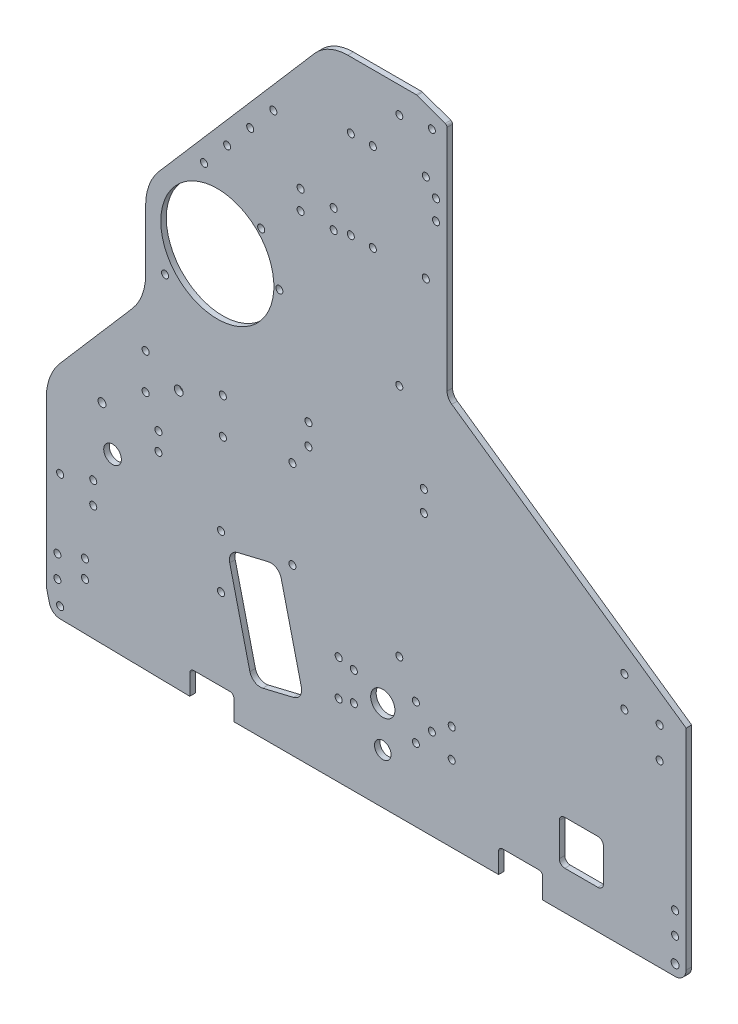
SolidWorks part; units mm, degrees
ref_plane "Front Plane" through (0, 0, 0) normal (0, 0, 1) x (1, 0, 0)
ref_plane "Top Plane" through (0, 0, 0) normal (0, 1, 0) x (1, 0, 0)
ref_plane "Right Plane" through (0, 0, 0) normal (1, 0, 0) x (0, 0, -1)
sketch "Sketch1" plane through (0, 0, 0) normal (0, 0, 1) x (1, 0, 0)
  line L0 (82.55, -20.32) -> (82.55, -6.35)
  line L2 (0, 0) -> (0, 157.48)
  line L4 (368.3, -20.32) -> (368.3, 106.68)
  line L5 (82.55, -6.35) -> (107.95, -6.35)
  line L6 (107.95, -6.35) -> (107.95, -20.32)
  line L7 (107.95, -20.32) -> (260.35, -20.32)
  line L8 (260.35, -20.32) -> (260.35, -6.35)
  line L9 (260.35, -6.35) -> (285.75, -6.35)
  line L10 (285.75, -6.35) -> (285.75, -20.32)
  line L11 (285.75, -20.32) -> (368.3, -20.32)
  line L12 (361.95, 12.7) -> (368.3, 12.7) construction
  line L13 (0, 0) -> (6.35, 0) construction
  line L14 (0.1896, -7.8901) -> (1.7771, -14.2401)
  line L15 (7.8295, -19.0491) -> (82.55, -20.32)
  line L16 (0, 0) -> (0, -6.35)
  line L17 (76.2, 128.905) -> (79.375, 128.905) construction
  line L18 (57.15, 118.5863) -> (101.6, 118.5862) construction
  line L19 (57.15, 118.5863) -> (57.15, 139.2238) construction
  line L20 (101.6, 118.5862) -> (101.6, 139.2237) construction
  line L21 (57.15, 139.2238) -> (101.6, 139.2237) construction
  line L22 (57.15, 118.5863) -> (101.6, 139.2237) construction
  line L23 (101.6, 118.5862) -> (57.15, 139.2238) construction
  line L25 (203.2, 59.805) -> (203.2, 194.805) construction
  line L26 (203.2, 194.805) -> (203.2, 329.805) construction
  line L27 (355.6, 332.105) -> (330.2, 332.105) construction
  line L28 (330.2, 332.105) -> (330.2, 217.805) construction
  line L29 (330.2, 217.805) -> (355.6, 217.805) construction
  line L30 (355.6, 217.805) -> (355.6, 332.105) construction
  line L31 (203.2, 344.805) -> (203.2, 194.805) construction
  line L32 (50.8, 332.105) -> (76.2, 332.105) construction
  line L33 (76.2, 332.105) -> (76.2, 217.805) construction
  line L34 (50.8, 217.805) -> (50.8, 332.105) construction
  line L35 (76.2, 217.805) -> (50.8, 217.805) construction
  line L36 (213.2, 344.805) -> (230.6638, 338.455)
  line L37 (203.2, 344.805) -> (161.925, 344.805)
  line L38 (203.2, 344.805) -> (213.2, 344.805)
  line L39 (348.5362, 344.805) -> (413.4623, 344.805)
  line L40 (348.5362, 344.805) -> (230.6638, 344.805) construction
  line L42 (161.925, 344.805) -> (0, 157.48)
  line L44 (230.6638, 338.455) -> (230.6638, 202.565)
  line L45 (230.6638, 202.565) -> (368.3, 106.68)
  line L46 (213.2, 344.805) -> (-141.0713, 344.805) construction
  circle A0 centre (6.35, 0) radius 2.032
  circle A1 centre (6.35, 12.7) radius 2.032
  circle A2 centre (361.95, 0) radius 2.032
  circle A3 centre (361.95, 12.7) radius 2.032
  arc A5 (1.7771, -14.2401) -> (7.8295, -19.0491) centre (7.9375, -12.7) ccw
  circle A6 centre (7.9375, -12.7) radius 2.032
  arc A7 (0, -6.35) -> (0.1896, -7.8901) centre (6.35, -6.35) ccw
  circle A8 centre (38.1, 78.105) radius 5.08
  circle A9 centre (76.2, 128.905) radius 2.54
  circle A10 centre (101.6, 118.5862) radius 2.032
  circle A11 centre (101.6, 139.2237) radius 2.032
  circle A12 centre (57.15, 139.2238) radius 2.032
  circle A13 centre (57.15, 118.5863) radius 2.032
  circle A15 centre (203.2, 59.805) radius 2
  circle A16 centre (203.2, 194.805) radius 2
  circle A17 centre (203.2, 329.805) radius 2
  circle A18 centre (63.5, 313.055) radius 2.032
  circle A20 centre (355.6, 332.105) radius 2.032
  circle A21 centre (330.2, 332.105) radius 2.032
  circle A22 centre (355.6, 217.805) radius 2.032
  circle A23 centre (330.2, 217.805) radius 2.032
  circle A24 centre (50.8, 332.105) radius 2.032
  circle A25 centre (76.2, 332.105) radius 2.032
  circle A26 centre (50.8, 217.805) radius 2.032
  circle A27 centre (76.2, 217.805) radius 2.032
  circle A28 centre (221.9319, 332.105) radius 2
  circle A29 centre (224.3138, 298.831) radius 2.032
  circle A30 centre (353.06, 100.7351) radius 2.032
  circle A31 centre (332.74, 115.9751) radius 2.032
  circle A32 centre (332.74, 98.1951) radius 2.032
  circle A33 centre (353.06, 82.9551) radius 2.032
  circle A34 centre (117.3562, 280.4276) radius 2.032
  circle A35 centre (104.0678, 265.0548) radius 2.032
  circle A36 centre (90.7795, 249.682) radius 2.032
  circle A38 centre (130.6445, 295.8004) radius 2.032
  circle A39 centre (68.326, 182.9237) radius 2.032
  circle A40 centre (224.3138, 287.401) radius 2.032
  point P82 (203.2, 344.805)
  point P83 (221.9319, 341.63)
  point P90 (368.3, 62.484)
  dimension "D6" = 4.064
  dimension "D10" = 6.35
  dimension "D11" = 4.064
  dimension "D17" = 38.1
  dimension "D27" = 4
  dimension "D31" = 4.064
  dimension "D32" = 41.275
  dimension "D36" = 4.064
  dimension "D47" = 39.624
  dimension "D48" = 4.064
  dimension "D25" = 5.08
  dimension "D26" = 4.064
  dimension "D52" = 4.064
  dimension "D65" = 4.064
  dimension "D69" = 10.16
  dimension "D2" = 127
  dimension "D3" = 13.97
  dimension "D4" = 25.4
  dimension "D5" = 152.4
  dimension "D7" = 12.7
  dimension "D8" = 6.35
  dimension "D9" = 20.32
  dimension "D12" = 12.7
  dimension "D13" = 1.5875
  dimension "D14" = 82.55
  dimension "D15" = 368.3
  dimension "D16" = 6.35
  dimension "D18" = 98.425
  dimension "D19" = 38.1
  dimension "D20" = 50.8
  dimension "D21" = 3.175
  dimension "D22" = 270
  dimension "D23" = 20.6375
  dimension "D24" = 44.45
  dimension "D28" = 135
  dimension "D29" = 12.7
  dimension "D30" = 15
  dimension "D33" = 63.5
  dimension "D34" = 27.4638
  dimension "D35" = 12.7
  dimension "D37" = 114.3
  dimension "D38" = 25.4
  dimension "D39" = 12.7
  dimension "D40" = 157.48
  dimension "D41" = 142.24
  dimension "D42" = 365.125
  dimension "D43" = 10
  dimension "D44" = 6.35
  dimension "D45" = 31.75
  dimension "D46" = 6.35
  dimension "D49" = 6.35
  dimension "D50" = 203.2
  dimension "D51" = 15.24
  dimension "D53" = 17.78
  dimension "D54" = 17.78
  dimension "D55" = 20.32
  dimension "D56" = 15.24
  dimension "D57" = 92.202
  dimension "D58" = 8.382
  dimension "D59" = 20.32
  dimension "D60" = 20.32
  dimension "D61" = 8.382
  dimension "D62" = 20.32
  dimension "D63" = 8.382
  dimension "D64" = 8.382
  dimension "D66" = 35.052
  dimension "D67" = 68.326
  dimension "D68" = 11.43
extrude "Boss-Extrude1" add sketch "Sketch1" along normal blind 3.175 contours L16 A7 L14 A5 L15 L2 A0 A1 A6 region at (171.4477, 119.565, 0)
fillet "Fillet1" radius 2.286 4 edges at (285.75, -6.35, 1.5875) (107.95, -6.35, 1.5875) (260.35, -6.35, 1.5875) (82.55, -6.35, 1.5875)
fillet "Fillet2" radius 6.35 1 edges at (230.6638, 202.565, 1.5875)
sketch "Sketch2" plane through (0, 0, 0) normal (0, 0, -1) x (-1, 0, 0)
  circle A0 centre (-100.5528, 71.086) radius 2.032 construction
  circle A1 centre (-100.5528, 40.606) radius 2.032 construction
  circle A2 centre (-22.225, 18.2025) radius 2.032 construction
  circle A3 centre (-22.225, 8.0425) radius 2.032 construction
  circle A4 centre (-100.5528, 71.086) radius 2.032
  circle A5 centre (-100.5528, 40.606) radius 2.032
  circle A6 centre (-22.225, 18.2025) radius 2.032
  circle A7 centre (-22.225, 8.0425) radius 2.032
extrude "Cut-Extrude1" cut sketch "Sketch2" against normal through all
fillet "Fillet3" radius 1.5875 2 edges at (230.6638, 338.455, 1.5875) (213.2, 344.805, 1.5875)
sketch "Sketch3" plane through (0, 0, 3.175) normal (0, 0, 1) x (1, 0, 0)
  line L0 (132.9524, 63.2646) -> (132.7215, 64.2281) construction
  line L1 (128.3814, 66.8897) -> (110.6828, 62.6472) construction
  line L2 (114.5132, 58.4237) -> (126.8822, 61.3887) construction
  line L3 (108.0212, 58.3071) -> (108.2522, 57.3436) construction
  line L4 (131.2006, 57.703) -> (140.0164, 20.9265) construction
  line L5 (144.0993, 16.7636) -> (132.9524, 63.2646) construction
  line L6 (108.2522, 57.3436) -> (119.3991, 10.8426) construction
  line L7 (121.1509, 16.4042) -> (112.3351, 53.1807) construction
  line L8 (119.3991, 10.8426) -> (119.6301, 9.8791) construction
  line L9 (144.3303, 15.8001) -> (144.0993, 16.7636) construction
  line L10 (137.8383, 15.6835) -> (125.4694, 12.7185) construction
  line L11 (123.9701, 7.2175) -> (141.6687, 11.4601) construction
  line L12 (132.9524, 63.2646) -> (132.7215, 64.2281)
  line L13 (128.3814, 66.8897) -> (110.6828, 62.6472)
  line L14 (114.5132, 58.4237) -> (126.8822, 61.3887)
  line L15 (108.0212, 58.3071) -> (108.2522, 57.3436)
  line L16 (131.2006, 57.703) -> (140.0164, 20.9265)
  line L17 (144.0993, 16.7636) -> (132.9524, 63.2646)
  line L18 (108.2522, 57.3436) -> (119.3991, 10.8426)
  line L19 (121.1509, 16.4042) -> (112.3351, 53.1807)
  line L20 (119.3991, 10.8426) -> (119.6301, 9.8791)
  line L21 (144.3303, 15.8001) -> (144.0993, 16.7636)
  line L22 (137.8383, 15.6835) -> (125.4694, 12.7185)
  line L23 (123.9701, 7.2175) -> (141.6687, 11.4601)
  line L24 (127.7894, 69.3598) -> (110.0908, 65.1172)
  line L25 (105.5512, 57.715) -> (105.7822, 56.7515)
  line L26 (105.7822, 56.7515) -> (116.9291, 10.2505)
  line L27 (116.9291, 10.2505) -> (117.16, 9.287)
  line L28 (124.5622, 4.7475) -> (142.2608, 8.99)
  line L29 (146.8003, 16.3922) -> (146.5694, 17.3557)
  line L30 (146.5694, 17.3557) -> (135.4225, 63.8567)
  line L31 (135.4225, 63.8567) -> (135.1915, 64.8202)
  line L32 (14.605, -0.1369) -> (103.7278, 32.3011) construction
  line L33 (14.605, -0.1369) -> (103.7278, 32.3011)
  line L34 (0, -6.35) -> (0, 157.48) construction
  line L35 (-39.6666, 74.7152) -> (103.7278, 126.9065) construction
  line L36 (26.9875, 46.9531) -> (26.9875, 59.6531) construction
  line L37 (107.95, -20.32) -> (260.35, -20.32) construction
  line L38 (64.5259, 92.5258) -> (64.5259, 102.9405) construction
  arc A0 (132.7215, 64.2281) -> (128.6308, 66.9403) centre (129.2206, 63.3889) ccw construction
  arc A1 (110.6828, 62.6472) -> (110.4377, 62.5791) centre (111.522, 59.1463) ccw construction
  arc A2 (128.6308, 66.9403) -> (128.3814, 66.8897) centre (129.2206, 63.3889) ccw construction
  arc A3 (110.4377, 62.5791) -> (108.0212, 58.3071) centre (111.522, 59.1463) ccw construction
  arc A4 (119.6301, 9.8791) -> (123.7207, 7.1669) centre (123.1309, 10.7183) ccw construction
  arc A5 (141.9139, 11.5281) -> (144.3303, 15.8001) centre (140.8295, 14.9609) ccw construction
  arc A6 (141.6687, 11.4601) -> (141.9139, 11.5281) centre (140.8295, 14.9609) ccw construction
  arc A7 (123.7207, 7.1669) -> (123.9701, 7.2175) centre (123.1309, 10.7183) ccw construction
  arc A8 (132.7215, 64.2281) -> (128.6308, 66.9403) centre (129.2206, 63.3889) ccw
  arc A9 (110.6828, 62.6472) -> (110.4377, 62.5791) centre (111.522, 59.1463) ccw
  arc A10 (128.6308, 66.9403) -> (128.3814, 66.8897) centre (129.2206, 63.3889) ccw
  arc A11 (110.4377, 62.5791) -> (108.0212, 58.3071) centre (111.522, 59.1463) ccw
  arc A12 (119.6301, 9.8791) -> (123.7207, 7.1669) centre (123.1309, 10.7183) ccw
  arc A13 (141.9139, 11.5281) -> (144.3303, 15.8001) centre (140.8295, 14.9609) ccw
  arc A14 (141.6687, 11.4601) -> (141.9139, 11.5281) centre (140.8295, 14.9609) ccw
  arc A15 (123.7207, 7.1669) -> (123.9701, 7.2175) centre (123.1309, 10.7183) ccw
  arc A16 (110.0908, 65.1172) -> (109.6726, 65.0012) centre (111.522, 59.1463) ccw
  arc A17 (109.6726, 65.0012) -> (105.5512, 57.715) centre (111.522, 59.1463) ccw
  arc A18 (117.16, 9.287) -> (124.1369, 4.6613) centre (123.1309, 10.7183) ccw
  arc A19 (124.1369, 4.6613) -> (124.5622, 4.7475) centre (123.1309, 10.7183) ccw
  arc A20 (142.2608, 8.99) -> (142.6789, 9.1061) centre (140.8295, 14.9609) ccw
  arc A21 (142.6789, 9.1061) -> (146.8003, 16.3922) centre (140.8295, 14.9609) ccw
  arc A22 (135.1915, 64.8202) -> (128.2147, 69.446) centre (129.2206, 63.3889) ccw
  arc A23 (128.2147, 69.446) -> (127.7894, 69.3598) centre (129.2206, 63.3889) ccw
  circle A26 centre (134.1438, 208.2281) radius 2.032 construction
  circle A33 centre (26.9875, 46.9531) radius 2.032
  circle A34 centre (26.9875, 59.6531) radius 2.032
  circle A35 centre (7.9375, 53.3031) radius 2.032
  circle A37 centre (32.0306, 100.8109) radius 31.75 construction
  circle A38 centre (32.0306, 100.8109) radius 2.286
  circle A39 centre (123.682, 233.4851) radius 2.032 construction
  circle A40 centre (64.5259, 102.9405) radius 2.032
  circle A41 centre (64.5259, 92.5258) radius 2.032
  circle A42 centre (134.1438, 208.2281) radius 2.032
  circle A43 centre (123.682, 233.4851) radius 2.032
  ellipse E0 centre (124.5974, 48.8487) end of major axis (128.5376, 61.3578) minor radius 6 (131.2006, 57.703) -> (126.8822, 61.3887) ccw construction
  ellipse E1 centre (122.2349, 48.2824) end of major axis (113.0518, 57.6456) minor radius 6 (114.5132, 58.4237) -> (112.3351, 53.1807) ccw construction
  ellipse E2 centre (127.7541, 25.2585) end of major axis (131.6942, 37.7675) minor radius 6 (121.1509, 16.4042) -> (125.4694, 12.7185) ccw construction
  ellipse E3 centre (130.1166, 25.8248) end of major axis (139.2998, 16.4616) minor radius 6 (137.8383, 15.6835) -> (140.0164, 20.9265) ccw construction
  ellipse E4 centre (124.5974, 48.8487) end of major axis (120.6573, 36.3397) minor radius 6 (131.2006, 57.703) -> (126.8822, 61.3887) ccw
  ellipse E5 centre (122.2349, 48.2824) end of major axis (131.4181, 38.9192) minor radius 6 (114.5132, 58.4237) -> (112.3351, 53.1807) ccw
  ellipse E6 centre (127.7541, 25.2585) end of major axis (131.6942, 37.7675) minor radius 6 (121.1509, 16.4042) -> (125.4694, 12.7185) ccw
  ellipse E7 centre (130.1166, 25.8248) end of major axis (139.2998, 16.4616) minor radius 6 (137.8383, 15.6835) -> (140.0164, 20.9265) ccw
  point P93 (26.9875, 53.3031)
  point P115 (32.0306, 100.8109)
  dimension "D3" = 63.5
  dimension "D4" = 4.572
  dimension "D8" = 4.064
  dimension "D2" = 88.9
  dimension "D5" = 7.9375
  dimension "D6" = 19.05
  dimension "D7" = 73.6231
  dimension "D9" = 12.7
  dimension "D10" = 10.4147
  dimension "D11" = 37.5384
  dimension "D12" = 45.5727
  dimension "D1" = 2.54
extrude "Cut-Extrude2" cut sketch "Sketch3" against normal through all contours A22 A23 L24 A16 A17 L25 L26 L27 A18 A19 L28 A20 A21 L29 L30 L31 A15 A12 L20 L18 L15 A11 A9 L13 A10 A8 L12 L17 L21 A13 A14 L23 | A12 A15 L23 A14 A13 L21 L17 L12 A8 A10 L13 A9 A11 L15 L18 L20 E7 L22 E6 L19 E5 L14 E4 L16 | L22 E7 L16 E4 L14 E5 L19 E6 | A38 | A41 | A40 | A35 | A34 | A33 | A43 | A42 region at (137.844, 39.8506, 3.175) region at (126.1758, 37.0536, 3.175) region at (128.1544, 68.6507, 3.175) region at (32.0306, 100.8109, 3.175) region at (64.5259, 102.9405, 3.175) region at (64.5259, 92.5258, 3.175)
sketch "Sketch4" plane through (0, 0, 3.175) normal (0, 0, 1) x (1, 0, 0)
  line L0 (57.15, 139.2238) -> (101.6, 139.2237) construction
  line L1 (168.275, 21.4312) -> (212.725, 21.4312) construction
  line L2 (168.275, 21.4312) -> (168.275, 42.0687) construction
  line L3 (168.275, 42.0687) -> (212.725, 42.0687) construction
  line L4 (212.725, 21.4312) -> (212.725, 42.0687) construction
  line L5 (168.275, 21.4312) -> (212.725, 42.0687) construction
  line L6 (168.275, 42.0687) -> (212.725, 21.4312) construction
  line L7 (57.15, 118.5863) -> (57.15, 139.2238) construction
  line L8 (107.95, -20.32) -> (260.35, -20.32) construction
  line L9 (193.675, 31.75) -> (177.005, 31.75) construction
  line L10 (190.5, 31.75) -> (193.675, 31.75) construction
  line L11 (6.35, 12.7) -> (361.95, 12.7) construction
  line L12 (107.95, -6.35) -> (107.95, -20.32) construction
  line L13 (193.675, 31.75) -> (220.6625, 31.75) construction
  line L14 (177.005, 23.4569) -> (177.005, 40.0431) construction
  line L15 (213.2, 44.805) -> (193.2, 44.805) construction
  line L16 (213.2, 44.805) -> (213.2, 344.805) construction
  line L17 (213.2, 344.805) -> (193.2, 344.805) construction
  line L18 (193.2, 44.805) -> (193.2, 344.805) construction
  line L19 (213.2, 44.805) -> (193.2, 344.805) construction
  line L20 (213.2, 344.805) -> (193.2, 44.805) construction
  line L21 (226.9319, 332.105) -> (226.9319, 31.75) construction
  line L22 (237.33, 40.0431) -> (233.3612, 40.0431) construction
  line L23 (237.33, 23.4569) -> (233.3612, 23.4569) construction
  circle A0 centre (168.275, 42.0687) radius 2.032
  circle A1 centre (212.725, 42.0687) radius 2.032
  circle A2 centre (212.725, 21.4312) radius 2.032
  circle A3 centre (168.275, 21.4312) radius 2.032
  circle A4 centre (193.675, 31.75) radius 6.985
  circle A7 centre (220.6625, 31.75) radius 14.2875 construction
  circle A8 centre (193.675, 31.75) radius 12.7 construction
  circle A9 centre (177.005, 40.0431) radius 2.032
  circle A10 centre (177.005, 23.4569) radius 2.032
  circle A11 centre (237.33, 40.0431) radius 2.032 construction
  circle A12 centre (237.33, 23.4569) radius 2.032 construction
  circle A13 centre (193.675, 8.4667) radius 4.7625
  circle A14 centre (221.9319, 31.75) radius 2.032
  circle A15 centre (221.9319, 31.75) radius 5 construction
  circle A16 centre (221.9319, 332.105) radius 5 construction
  circle A17 centre (233.3612, 23.4569) radius 2.032
  circle A18 centre (233.3612, 40.0431) radius 2.032
  point P0 (190.5, 31.75)
  point P26 (203.2, 194.805)
  point P38 (177.005, 31.75)
  dimension "D1" = 4.064
  dimension "D4" = 13.97
  dimension "D7" = 9.525
  dimension "D10" = 25.4
  dimension "D11" = 28.575
  dimension "D16" = 10
  dimension "D17" = 4.064
  dimension "D18" = 10
  dimension "D2" = 52.07
  dimension "D3" = 3.175
  dimension "D5" = 82.55
  dimension "D6" = 26.9875
  dimension "D8" = 20
  dimension "D9" = 300
  dimension "D12" = 16.67
  dimension "D13" = 16.5862
  dimension "D14" = 60.325
  dimension "D15" = 23.2833
  dimension "D19" = 3.9688
extrude "Cut-Extrude3" cut sketch "Sketch4" against normal through all
sketch "Sketch5" plane through (0, 0, 0) normal (0, 0, -1) x (-1, 0, 0)
  line L0 (-57.15, 223.5947) -> (-57.15, 165.3337)
  line L1 (-161.925, 344.805) -> (-52.7201, 218.4699) construction
  line L2 (-57.15, 165.3337) -> (0, 99.219)
  line L3 (0, -6.35) -> (0, 157.48) construction
  line L5 (-50.4199, 215.8089) -> (0, 157.48) construction
  line L6 (-57.15, 223.5947) -> (0, 157.48)
  line L7 (0, 157.48) -> (0, 99.219)
  line L8 (-361.95, -13.97) -> (-368.3, -13.97) construction
  line L9 (-361.95, -13.97) -> (-361.95, -20.32) construction
  line L10 (-285.75, -20.32) -> (-368.3, -20.32) construction
  line L11 (-368.3, -20.32) -> (-368.3, 106.68) construction
  circle A0 centre (-98.425, 208.2281) radius 32.5437
  circle A2 centre (-361.95, -13.97) radius 2.286
  dimension "D3" = 65.0875
  dimension "D7" = 4.572
  dimension "D1" = 38.1
  dimension "D2" = 57.15
  dimension "D4" = 41.275
  dimension "D5" = 41.275
  dimension "D6" = 6.35
extrude "Cut-Extrude5" cut sketch "Sketch5" against normal through all contours A0 | L7 L6 L0 L2 | A2 region at (28.575, 161.4068, 0) region at (98.425, 208.2281, 0)
fillet "Fillet4" radius 31.75 3 edges at (0, 99.219, 1.5875) (57.15, 165.3337, 1.5875) (57.15, 223.5947, 1.5875)
sketch "Sketch6" plane through (0, 0, 3.175) normal (0, 0, 1) x (1, 0, 0)
  line L0 (285.75, -20.32) -> (368.3, -20.32) construction
  line L1 (298.45, 27.305) -> (317.5, 27.305)
  line L2 (295.275, 24.13) -> (295.275, 5.08)
  line L3 (298.45, 1.905) -> (317.5, 1.905)
  line L4 (320.675, 24.13) -> (320.675, 5.08)
  line L5 (295.275, 27.305) -> (320.675, 1.905) construction
  line L6 (295.275, 1.905) -> (320.675, 27.305) construction
  line L7 (368.3, -20.32) -> (368.3, 106.68) construction
  arc A0 (295.275, 5.08) -> (298.45, 1.905) centre (298.45, 5.08) ccw
  arc A1 (317.5, 1.905) -> (320.675, 5.08) centre (317.5, 5.08) ccw
  arc A2 (317.5, 27.305) -> (320.675, 24.13) centre (317.5, 24.13) cw
  arc A3 (298.45, 27.305) -> (295.275, 24.13) centre (298.45, 24.13) ccw
  point P0 (307.975, 14.605)
  dimension "D2" = 3.175
  dimension "D1" = 25.4
  dimension "D3" = 22.225
  dimension "D4" = 47.625
extrude "Cut-Extrude6" cut sketch "Sketch6" against normal through all
fillet "Fillet5" radius 25.4 1 edges at (161.925, 344.805, 1.5875)
sketch "Sketch8" plane through (0, 0, 0) normal (0, 0, -1) x (-1, 0, 0)
  circle A0 centre (-187.96, 306.705) radius 2.032 construction
  arc A1 (-176.3652, 304.9998) -> (-176.3652, 308.4102) centre (-175.26, 306.705) ccw construction
  arc A2 (-219.0586, 304.7695) -> (-219.0586, 308.6405) centre (-218.44, 306.705) ccw construction
  circle A3 centre (-205.74, 306.705) radius 2.032 construction
  arc A4 (-219.0586, 253.9695) -> (-219.0586, 257.8405) centre (-218.44, 255.905) ccw construction
  circle A5 centre (-205.74, 255.905) radius 2.032 construction
  circle A6 centre (-187.96, 255.905) radius 2.032 construction
  arc A7 (-176.3652, 254.1998) -> (-176.3652, 257.6102) centre (-175.26, 255.905) ccw construction
  circle A8 centre (-187.96, 306.705) radius 2.032
  arc A9 (-176.3652, 304.9998) -> (-176.3652, 308.4102) centre (-175.26, 306.705) ccw
  arc A10 (-219.0586, 304.7695) -> (-219.0586, 308.6405) centre (-218.44, 306.705) ccw
  circle A11 centre (-205.74, 306.705) radius 2.032
  arc A12 (-219.0586, 253.9695) -> (-219.0586, 257.8405) centre (-218.44, 255.905) ccw
  circle A13 centre (-205.74, 255.905) radius 2.032
  circle A14 centre (-187.96, 255.905) radius 2.032
  arc A15 (-176.3652, 254.1998) -> (-176.3652, 257.6102) centre (-175.26, 255.905) ccw
  circle A16 centre (-218.44, 306.705) radius 2.032
  circle A17 centre (-175.26, 306.705) radius 2.032
  circle A18 centre (-175.26, 255.905) radius 2.032
  circle A19 centre (-218.44, 255.905) radius 2.032
  circle A20 centre (-218.44, 306.705) radius 3.9688
  circle A21 centre (-205.74, 306.705) radius 3.9688
  circle A22 centre (-175.26, 306.705) radius 3.9687
  circle A23 centre (-218.44, 255.905) radius 3.9688
  circle A24 centre (-205.74, 255.905) radius 3.9688
  circle A25 centre (-187.96, 255.905) radius 3.9687
  circle A26 centre (-175.26, 255.905) radius 3.9687
  circle A27 centre (-187.96, 306.705) radius 3.9687
  dimension "D1" = 7.9375
extrude "Cut-Extrude7" cut sketch "Sketch8" against normal through all contours A10 A16 | A9 A17 | A15 A18 | A12 A19 | A8 | A14 region at (175.26, 306.705, 0) region at (218.44, 306.705, 0) region at (218.44, 255.905, 0) region at (175.26, 255.905, 0)
sketch "Sketch10" plane through (0, 0, 3.175) normal (0, 0, 1) x (1, 0, 0)
  circle A4 centre (141.6425, 74.6844) radius 2.032 construction
  circle A5 centre (141.6425, 125.4844) radius 2.032 construction
  circle A6 centre (141.6425, 74.6844) radius 2.032
  circle A7 centre (141.6425, 125.4844) radius 2.032
extrude "Cut-Extrude8" cut sketch "Sketch10" against normal through all
fillet "Fillet6" radius 6.35 1 edges at (368.3, -20.32, 1.5875)
sketch "Sketch11" plane through (0, 0, 3.175) normal (0, 0, 1) x (1, 0, 0)
  ellipse E4 centre (150.8814, 138.43) end of major axis (150.8814, 140.462) minor radius 2.032
  ellipse E5 centre (150.8814, 150.495) end of major axis (150.8814, 152.527) minor radius 2.032
  ellipse E6 centre (217.3024, 150.495) end of major axis (217.3024, 152.527) minor radius 2.032
  ellipse E7 centre (217.3024, 138.43) end of major axis (217.3024, 140.462) minor radius 2.032
extrude "Cut-Extrude9" cut sketch "Sketch11" against normal through all
sketch "Sketch12" plane through (0, 0, 0) normal (0, 0, -1) x (-1, 0, 0)
  line L0 (-173.5432, 344.805) -> (-212.9203, 344.805) construction
  circle A0 centre (-165.4175, 264.635) radius 2.032
  circle A1 centre (-203.2, 329.805) radius 2 construction
  circle A2 centre (-165.4175, 253.5225) radius 2.032
  circle A3 centre (-146.3675, 253.5225) radius 2.032
  circle A4 centre (-146.3675, 264.635) radius 2.032
  point P12 (0, 0)
  point P13 (0, 0)
  point P14 (0, 0)
  point P15 (0, 0)
  dimension "D1" = 80.17
  dimension "D2" = 4.064
  dimension "D3" = 37.7825
  dimension "D4" = 11.1125
  dimension "D5" = 19.05
extrude "Cut-Extrude10" cut sketch "Sketch12" against normal through all
sketch "Sketch13" plane through (0, 0, 0) normal (0, 0, -1) x (-1, 0, 0)
  line L0 (-190.2532, 261.8265) -> (-167.7107, 270.5564)
  line L1 (-140.0175, 264.635) -> (-140.0175, 253.5225)
  line L2 (-166.0849, 247.2077) -> (-188.6274, 249.5902)
  line L3 (-165.4175, 247.1725) -> (-146.3675, 247.1725)
  line L4 (-165.4175, 270.985) -> (-146.3675, 270.985)
  circle A0 centre (-146.3675, 264.635) radius 2.032 construction
  circle A1 centre (-146.3675, 253.5225) radius 2.032 construction
  circle A2 centre (-165.4175, 253.5225) radius 2.032 construction
  circle A3 centre (-165.4175, 264.635) radius 2.032 construction
  circle A4 centre (-175.26, 255.905) radius 2.032 construction
  circle A5 centre (-187.96, 255.905) radius 2.032 construction
  circle A6 centre (-146.3675, 264.635) radius 2.032
  circle A7 centre (-146.3675, 253.5225) radius 2.032
  circle A8 centre (-165.4175, 253.5225) radius 2.032
  circle A9 centre (-165.4175, 264.635) radius 2.032
  circle A10 centre (-175.26, 255.905) radius 2.032
  circle A11 centre (-187.96, 255.905) radius 2.032
  arc A12 (-188.6274, 249.5902) -> (-190.2532, 261.8265) centre (-187.96, 255.905) cw
  arc A13 (-167.7107, 270.5564) -> (-165.4175, 270.985) centre (-165.4175, 264.635) cw
  arc A14 (-166.0849, 247.2077) -> (-165.4175, 247.1725) centre (-165.4175, 253.5225) ccw
  arc A15 (-146.3675, 247.1725) -> (-140.0175, 253.5225) centre (-146.3675, 253.5225) ccw
  arc A16 (-146.3675, 270.985) -> (-140.0175, 264.635) centre (-146.3675, 264.635) cw
  dimension "D1" = 6.35
extrude "Boss-Extrude2" [suppressed] add sketch "Sketch13" along normal blind 6.35 separate body
